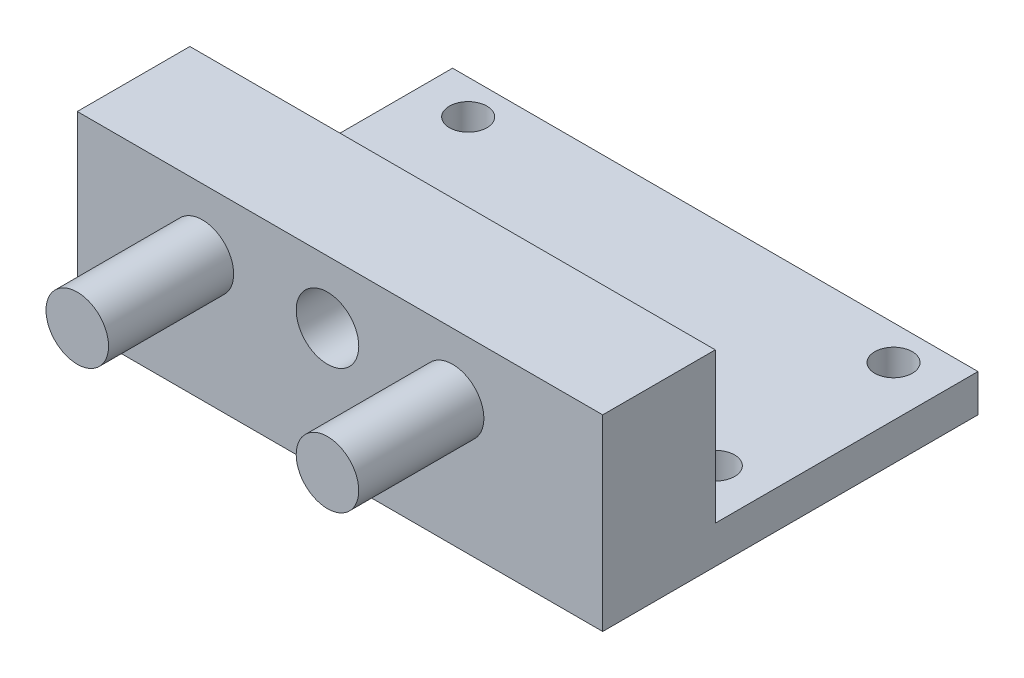
SolidWorks part; units mm, degrees
ref_plane "Front Plane" through (0, 0, 0) normal (0, 0, 1) x (1, 0, 0)
ref_plane "Top Plane" through (0, 0, 0) normal (0, 1, 0) x (1, 0, 0)
ref_plane "Right Plane" through (0, 0, 0) normal (1, 0, 0) x (0, 0, -1)
sketch "Sketch1" plane through (0, 0, 0) normal (0, 1, 0) x (1, 0, 0)
  line L0 (-21, -6) -> (21, -6)
  line L1 (-21, -15) -> (21, -15)
  line L2 (-21, -15) -> (-21, 15)
  line L3 (-21, 15) -> (21, 15)
  line L4 (21, -15) -> (21, 15)
  line L5 (-21, -15) -> (21, 15) construction
  line L6 (-21, 15) -> (21, -15) construction
  line L7 (0, -15) -> (0, 15) construction
  circle A0 centre (-17, 12.2485) radius 1.5
  circle A1 centre (-17.0441, -2) radius 1.5
  circle A2 centre (17.0441, -2) radius 1.5
  circle A3 centre (17, 12.2485) radius 1.5
  point P0 (0, 0)
  dimension "D3" = 3
  dimension "D4" = 3
  dimension "D1" = 42
  dimension "D2" = 30
  dimension "D5" = 4
  dimension "D6" = 2.7515
  dimension "D7" = 17
  dimension "D8" = 9
extrude "Boss-Extrude1" add sketch "Sketch1" along normal blind 3 contours L0 L4 L3 L2 A2 A1 A0 A3 region at (0, 0, -4.4793)
extrude "Boss-Extrude2" add sketch "Sketch1<3>" along normal blind 15 contours L1 L4 L0 L2 region at (0, 0, 10.5)
sketch "Sketch1<3>" plane through (0, 0, 0) normal (0, 1, 0) x (1, 0, 0) same geometry as "Sketch1"
sketch "Sketch2" plane through (0, 0, 15) normal (0, 0, 1) x (1, 0, 0)
  line L0 (-21, 0) -> (21, 0) construction
  line L1 (-21, 15) -> (-21, 0) construction
  circle A0 centre (-11, 10) radius 2.5
  circle A1 centre (-1, 10) radius 2.5
  circle A2 centre (9, 10) radius 2.5
  dimension "D1" = 5
  dimension "D2" = 10
  dimension "D3" = 10
  dimension "D4" = 3
extrude "Boss-Extrude3" add sketch "Sketch2" along normal blind 10 contours A2 | A0 region at (9, 10, 15)
extrude "Cut-Extrude2" cut sketch "Sketch2<4>" against normal blind 10 contours A1 region at (-1, 10, 15)
sketch "Sketch2<4>" plane through (0, 0, 15) normal (0, 0, 1) x (1, 0, 0) same geometry as "Sketch2"
